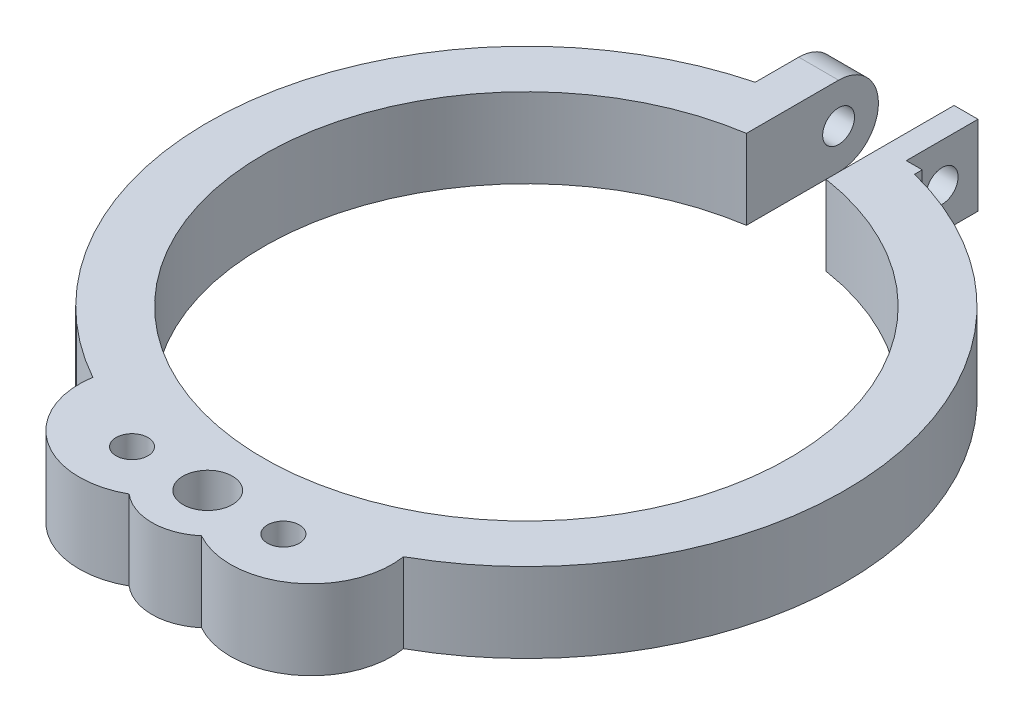
SolidWorks part; units mm, degrees
ref_plane "Alzado" through (0, 0, 0) normal (0, 0, 1) x (1, 0, 0)
ref_plane "Planta" through (0, 0, 0) normal (0, 1, 0) x (1, 0, 0)
ref_plane "Vista lateral" through (0, 0, 0) normal (1, 0, 0) x (0, 0, -1)
sketch "Croquis1" plane through (0, 0, 0) normal (0, 1, 0) x (1, 0, 0)
  line L0 (0, 0) -> (10, 0)
  line L1 (0, 0) -> (-10, 0)
  line L2 (10, 0) -> (10, 31.4484)
  line L3 (-10, 0) -> (-10, 31.4484)
  line L4 (10, 31.4484) -> (10, 38.7298)
  line L5 (-10, 31.4484) -> (-10, 38.7298)
  line L6 (5, 0) -> (5, 32.619)
  line L7 (5, 32.619) -> (5, 39.6863)
  line L8 (-5, 0) -> (-5, 32.619)
  line L9 (-5, 32.619) -> (-5, 39.6863)
  line L10 (5, 32.619) -> (10, 32.619)
  line L11 (-5, 39.6863) -> (-10, 39.6863)
  line L12 (-10, 39.6863) -> (-10, 38.7298)
  line L13 (5, 39.6863) -> (10, 39.6863)
  line L14 (10, 39.6863) -> (10, 38.7298)
  circle A0 centre (0, 0) radius 33
  circle A1 centre (0, 0) radius 40
extrude "Saliente-Extruir1" add sketch "Croquis1" along normal blind 10 contours L5 A1 L4 A0 | L9 A1 L5 A0 | L4 A1 L7 L10 | A1 L14 L13 | A1 L11 L12 | A0 L4 L10 region at (7.4401, 0, -35.9468) region at (8.4426, 0, -32.2495) region at (-7.5124, 0, -35.68) region at (11.1224, 0, -32.0337) region at (8.4409, 0, -39.384) region at (-8.4409, 0, -39.384)
sketch "Croquis2" plane through (0, 10, 0) normal (0, 1, 0) x (1, 0, 0)
  circle A2 centre (0, -40) radius 7
  arc A3 (-10, 38.7298) -> (10, 38.7298) centre (0, 0) ccw construction
  circle A4 centre (9.5, -36.5) radius 10.1242
  circle A5 centre (-9.5, -36.5) radius 10.1242
  arc M5 (-10, 38.7298) -> (10, 38.7298) centre (0, 0) ccw
extrude "Saliente-Extruir2" add sketch "Croquis2" against normal blind 10 contours A5 A2 M5 | A5 A2 M5 | A4 A5 A2 | A4 A2 M5 | A2 A4 M5 region at (3.9377, 10, 41.8856) region at (12.636, 10, 41.5711) region at (0, 10, 44.5871) region at (-3.9377, 10, 41.8856) region at (-12.636, 10, 41.5711)
sketch "Croquis3" plane through (-10, 0, 0) normal (-1, 0, 0) x (0, 0, 1)
  line L0 (-39.6863, 5) -> (-44.1863, 5)
  line L1 (-39.6863, 10) -> (-42.6863, 10)
  line L2 (-39.6863, 10) -> (-39.6863, 0)
  line L3 (-39.6863, 0) -> (-42.6863, 0)
  line L5 (-44.1863, 5) -> (-44.1863, 10)
  line L6 (-44.1863, 10) -> (-42.6863, 10)
  line L7 (-44.1863, 5) -> (-44.1863, 0)
  line L8 (-44.1863, 0) -> (-42.6863, 0)
  circle A0 centre (-44.1863, 5) radius 2
  circle A1 centre (-44.1863, 5) radius 5
  line M4 (-39.6863, 10) -> (-39.6863, 0)
extrude "Saliente-Extruir3" add sketch "Croquis3" against normal blind 5 contours A0 L1 M4 | A0 L3 M4 | L2 A1 L5 A0 L0 | L7 A1 L0 A0 M4 | L5 A1 L7 A0 region at (-10, 2.5636, -41.9305) region at (-10, 7.4364, -41.9305) region at (-10, 9.2198, -40.7384) region at (-10, 0.7802, -40.7384) region at (-10, 5, -46.5509)
sketch "Croquis5" plane through (5, 0, 0) normal (-1, 0, 0) x (0, 0, 1)
  line L0 (-39.6863, 10) -> (-48.6863, 10)
  line L1 (-48.6863, 10) -> (-48.6863, 0)
  line L2 (-48.6863, 0) -> (-39.6863, 0)
  line L3 (-39.6863, 0) -> (-39.6863, 10)
  circle A0 centre (-44.1863, 5) radius 2
extrude "Saliente-Extruir4" add sketch "Croquis5" against normal blind 3
sketch "Croquis8" plane through (0, 10, 0) normal (0, 1, 0) x (1, 0, 0)
  circle A0 centre (9.5, -40) radius 2
  circle A1 centre (-9.5, -40) radius 2
extrude "Cortar-Extruir1" cut sketch "Croquis8" against normal blind 10
sketch "Croquis10" plane through (0, 10, 0) normal (0, 1, 0) x (1, 0, 0)
  circle A0 centre (0, -40) radius 3.1
extrude "Cortar-Extruir3" cut sketch "Croquis10" against normal blind 10
